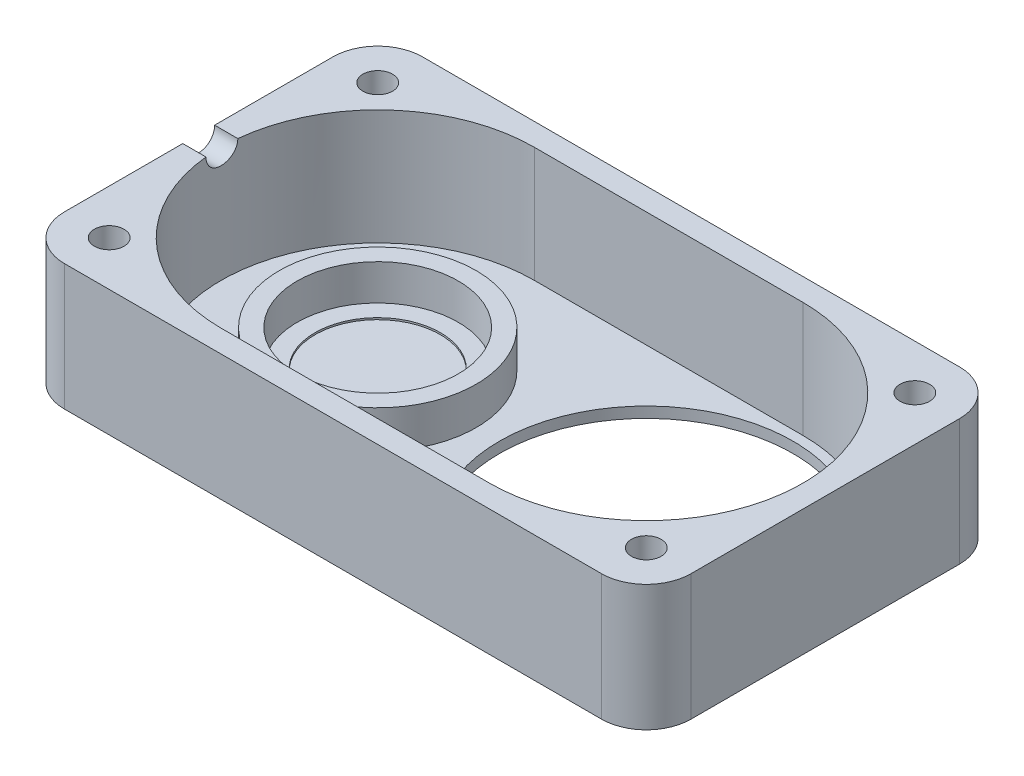
SolidWorks part; units mm, degrees
ref_plane "Front Plane" through (0, 0, 0) normal (0, 0, 1) x (1, 0, 0)
ref_plane "Top Plane" through (0, 0, 0) normal (0, 1, 0) x (1, 0, 0)
ref_plane "Right Plane" through (0, 0, 0) normal (1, 0, 0) x (0, 0, -1)
sketch "Sketch1" plane through (0, 0, 0) normal (0, 1, 0) x (1, 0, 0)
  line L0 (38.1, 19.05) -> (38.1, 25.4) construction
  line L1 (-19.05, -25.4) -> (57.15, -25.4)
  line L2 (-25.4, -19.05) -> (-25.4, 19.05)
  line L3 (-19.05, 25.4) -> (57.15, 25.4)
  line L4 (63.5, -19.05) -> (63.5, 19.05)
  line L5 (-25.4, -25.4) -> (63.5, 25.4) construction
  line L6 (-25.4, 25.4) -> (63.5, -25.4) construction
  line L7 (57.15, 0) -> (63.5, 0) construction
  line L9 (-7.62, -11.176) -> (7.62, -11.176) construction
  line L10 (-7.62, -11.176) -> (-7.62, 11.176) construction
  line L11 (-7.62, 11.176) -> (7.62, 11.176) construction
  line L12 (7.62, -11.176) -> (7.62, 11.176) construction
  line L13 (-7.62, -11.176) -> (7.62, 11.176) construction
  line L14 (-7.62, 11.176) -> (7.62, -11.176) construction
  circle A0 centre (0, 0) radius 19.05 construction
  circle A1 centre (38.1, 0) radius 19.05 construction
  circle A2 centre (38.1, 0) radius 12.7 construction
  circle A3 centre (38.1, 0) radius 20.828
  arc A4 (-25.4, 19.05) -> (-19.05, 25.4) centre (-19.05, 19.05) cw
  arc A5 (-19.05, -25.4) -> (-25.4, -19.05) centre (-19.05, -19.05) cw
  arc A6 (57.15, -25.4) -> (63.5, -19.05) centre (57.15, -19.05) ccw
  arc A7 (57.15, 25.4) -> (63.5, 19.05) centre (57.15, 19.05) cw
  circle A8 centre (-19.05, 19.05) radius 2.1
  circle A9 centre (-19.05, -19.05) radius 2.1
  circle A10 centre (57.15, -19.05) radius 2.1
  circle A11 centre (57.15, 19.05) radius 2.1
  point P6 (19.05, 0)
  dimension "D1" = 38.1
  dimension "D2" = 38.1
  dimension "D3" = 50.8
  dimension "D7" = 25.4
  dimension "D8" = 41.656
  dimension "D9" = 6.35
  dimension "D10" = 4.2
  dimension "D4" = 88.9
  dimension "D5" = 15.24
  dimension "D6" = 22.352
extrude "Boss-Extrude1" add sketch "Sketch1" along normal blind 17.8791
sketch "Sketch2" plane through (0, 17.8791, 0) normal (0, 1, 0) x (1, 0, 0)
  line L0 (0, 22.225) -> (38.1, 22.225)
  line L1 (38.1, -22.225) -> (0, -22.225)
  arc A0 (0, 22.225) -> (0, -22.225) centre (0, 0) ccw
  arc A1 (38.1, -22.225) -> (38.1, 22.225) centre (38.1, 0) ccw
  dimension "D1" = 44.45
extrude "Cut-Extrude1" cut sketch "Sketch2" against normal offset from surface (16.3551 mm away) 1.524 up to face at (57.15, 0, 21.15)
sketch "Sketch3" plane through (0, 1.524, 0) normal (0, 1, 0) x (1, 0, 0)
  circle A0 centre (0, 0) radius 13.97
  circle A1 centre (0, 0) radius 8.89
  dimension "D1" = 27.94
  dimension "D2" = 17.78
extrude "Boss-Extrude2" add sketch "Sketch3" along normal blind 0.254
sketch "Sketch4" plane through (0, 1.778, 0) normal (0, 1, 0) x (1, 0, 0)
  circle A0 centre (0, 0) radius 11.43
  circle A1 centre (0, 0) radius 13.97 construction
  circle A2 centre (0, 0) radius 13.97
  dimension "D1" = 22.86
extrude "Boss-Extrude3" add sketch "Sketch4" along normal blind 5.08
sketch "Sketch6" plane through (-25.4, 0, 0) normal (-1, 0, 0) x (0, 0, 1)
  line L0 (-19.05, 17.8791) -> (19.05, 17.8791) construction
  circle A0 centre (0, 17.8791) radius 2.2606
  dimension "D1" = 4.5212
extrude "Cut-Extrude2" cut sketch "Sketch6" against normal up to next
sketch "Sketch7" plane through (0, 0, 0) normal (0, -1, 0) x (1, 0, 0)
  circle A0 centre (-19.05, 19.05) radius 3.75
  circle A1 centre (-19.05, -19.05) radius 3.75
  circle A2 centre (57.15, -19.05) radius 3.75
  circle A3 centre (57.15, 19.05) radius 3.75
  dimension "D1" = 7.5
extrude "Cut-Extrude3" cut sketch "Sketch7" against normal blind 4.5
sketch "Sketch8" plane through (0, 0, 0) normal (0, -1, 0) x (1, 0, 0)
  line L0 (20.0168, 10.3347) -> (14.3924, 15.4756)
  line L1 (14.3924, 15.4756) -> (20.5616, 22.225)
  line L2 (20.5616, 22.225) -> (26.186, 17.084)
  line L3 (17.477, 18.8503) -> (38.1, 0) construction
  line L4 (0, 22.225) -> (38.1, 22.225) construction
  circle A0 centre (38.1, 0) radius 20.828 construction
  arc A1 (26.186, 17.084) -> (20.0168, 10.3347) centre (38.1, 0) ccw
  point P8 (22.7265, 14.0521)
  dimension "D1" = 9.144
  dimension "D2" = 7.112
extrude "Cut-Extrude4" cut sketch "Sketch8" against normal through all
fillet "Fillet1" radius 2.54 2 edges at (20.0168, 0.762, 10.3347) (26.186, 0.762, 17.084)
